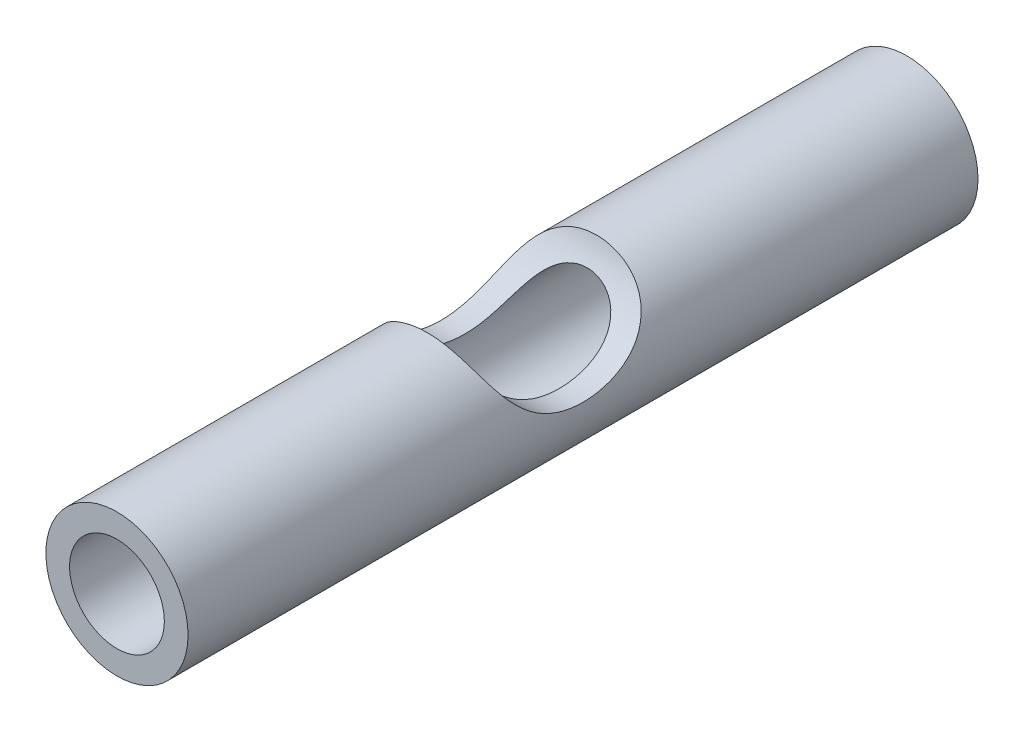
SolidWorks part; units mm, degrees
ref_plane "Front Plane" through (0, 0, 0) normal (0, 0, 1) x (1, 0, 0)
ref_plane "Top Plane" through (0, 0, 0) normal (0, 1, 0) x (1, 0, 0)
ref_plane "Right Plane" through (0, 0, 0) normal (1, 0, 0) x (0, 0, -1)
sketch "Sketch1" plane through (0, 0, 0) normal (0, 0, 1) x (1, 0, 0)
  circle A0 centre (0, 0) radius 12
  circle A1 centre (0, 0) radius 18
  dimension "D1" = 24
  dimension "D2" = 36
extrude "Boss-Extrude1" add sketch "Sketch1" along normal blind 100 and the other way blind 100
sketch "Sketch2" plane through (0, 0, 0) normal (1, 0, 0) x (0, 0, -1)
  circle A0 centre (0, 23) radius 22
  dimension "D1" = 44
  dimension "D2" = 23
extrude "Cut-Extrude1" cut sketch "Sketch2" against normal through all both and the other way through all contours A0
